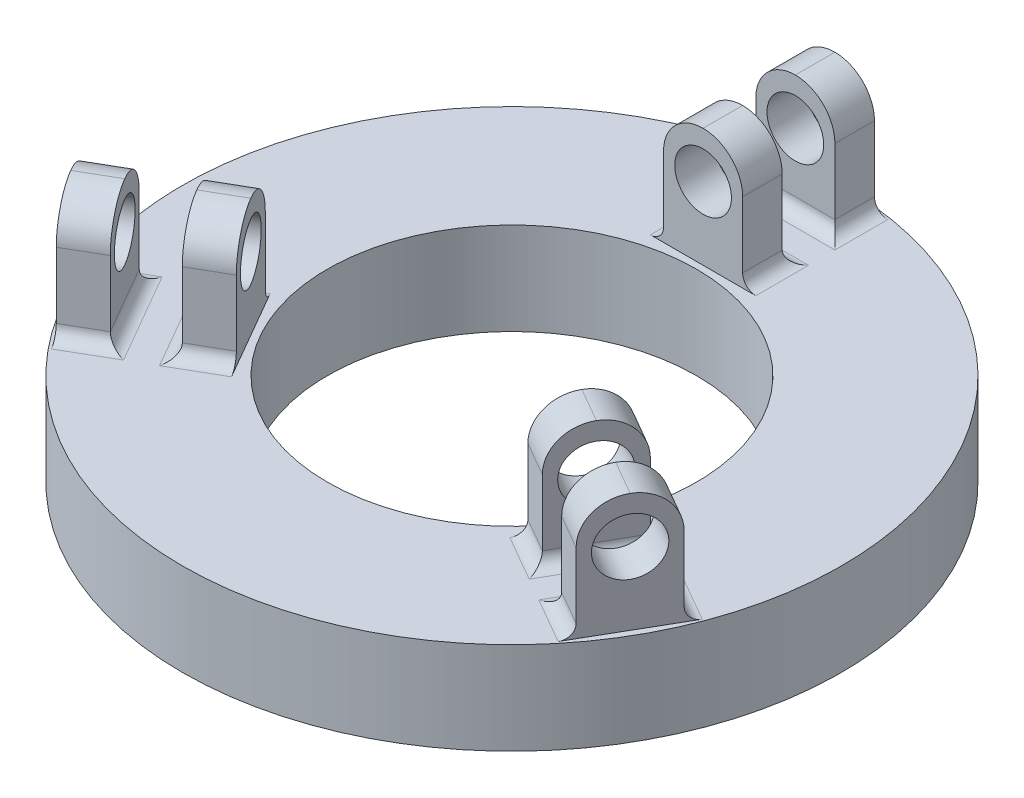
SolidWorks part; units mm, degrees
ref_plane "Front Plane" through (0, 0, 0) normal (0, 0, 1) x (1, 0, 0)
ref_plane "Top Plane" through (0, 0, 0) normal (0, 1, 0) x (1, 0, 0)
ref_plane "Right Plane" through (0, 0, 0) normal (1, 0, 0) x (0, 0, -1)
sketch "Sketch1" plane through (0, 0, 0) normal (0, 1, 0) x (1, 0, 0)
  line L0 (0, 0) -> (0, 14) construction
  circle A1 centre (0, 0) radius 14
  circle A7 centre (0, 0) radius 25
  point P4 (0, 22.2656)
  point P32 (0, 0)
  dimension "D1" = 50
  dimension "D2" = 28
extrude "Boss-Extrude1" add sketch "Sketch1" along normal blind 7
sketch "Sketch3" plane through (0, 7, 0) normal (0, 1, 0) x (1, 0, 0)
  line L0 (0, 21.4129) -> (0, 10.5871) construction
  line L6 (-3, 17.5) -> (3, 17.5)
  line L11 (-3, 17.5) -> (-3, 14.5)
  line L12 (-3, 14.5) -> (3, 14.5)
  line L13 (3, 17.5) -> (3, 14.5)
  line L14 (-3, 17.5) -> (3, 14.5) construction
  line L15 (-3, 14.5) -> (3, 17.5) construction
  line L16 (-3, 21.5) -> (3, 21.5)
  line L17 (-3, 21.5) -> (-3, 24.5)
  line L18 (-3, 24.5) -> (3, 24.5)
  line L19 (3, 21.5) -> (3, 24.5)
  line L20 (-3, 21.5) -> (3, 24.5) construction
  line L21 (-3, 24.5) -> (3, 21.5) construction
  point P0 (0, 16)
  point P5 (0, 23)
  point P13 (0, 0)
  dimension "D1" = 3
  dimension "D2" = 6
  dimension "D3" = 3
  dimension "D4" = 6
  dimension "D5" = 4
  dimension "D6" = 16
extrude "Boss-Extrude2" add sketch "Sketch3" along normal blind 9
sketch "Sketch4" plane through (0, 0, -14.5) normal (0, 0, 1) x (1, 0, 0)
  line L0 (-3, 16) -> (3, 16) construction
  circle A0 centre (0, 12.5) radius 2.15
  dimension "D1" = 4.3
  dimension "D2" = 3.5
extrude "Cut-Extrude1" cut sketch "Sketch4" against normal blind 10
fillet "Fillet1" radius 3 4 edges at (3, 16, -16) (-3, 16, -16) (-3, 16, -23) (3, 16, -23)
fillet "Fillet2" radius 1 6 edges at (0, 7, -17.5) (0, 7, -21.5) (3, 7, -16) (-3, 7, -16) (-3, 7, -23) (3, 7, -23)
pattern_circular "CirPattern1" count 3 over 360 about axis through (0, 7, 0) along (0, -1, 0) of "Boss-Extrude2", "Cut-Extrude1", "Fillet1", "Fillet2"
